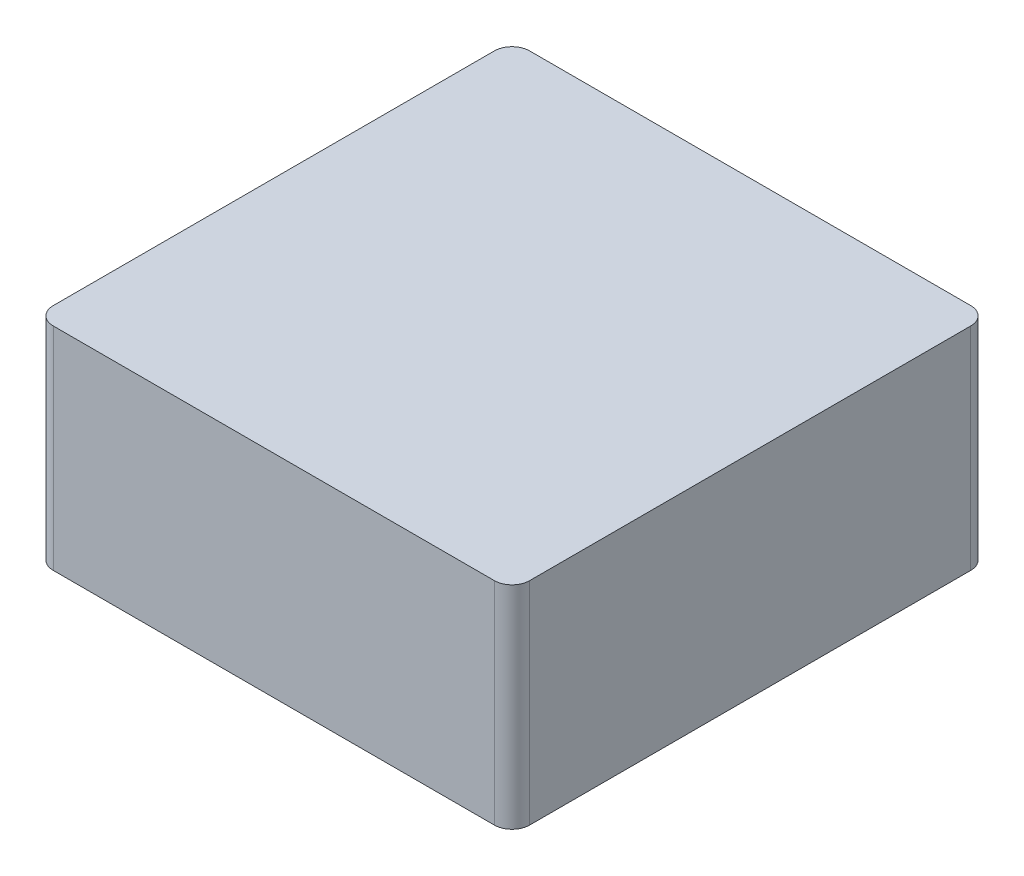
SolidWorks part; units mm, degrees
ref_plane "前视基准面" through (0, 0, 0) normal (0, 0, 1) x (1, 0, 0)
ref_plane "上视基准面" through (0, 0, 0) normal (0, 1, 0) x (1, 0, 0)
ref_plane "右视基准面" through (0, 0, 0) normal (1, 0, 0) x (0, 0, -1)
sketch "草图1" plane through (0, 0, 0) normal (0, 1, 0) x (1, 0, 0)
  line L1 (-27, 27) -> (27, 27)
  line L2 (-27, 27) -> (-27, -27)
  line L3 (-27, -27) -> (27, -27)
  line L4 (27, 27) -> (27, -27)
  line L5 (0, -27) -> (0, 27) construction
  line L6 (-27, 0) -> (27, 0) construction
  point P0 (0, 0)
  point P6 (-28.1217, -26.8398)
  dimension "D1" = 54
extrude "凸台-拉伸1" add sketch "草图1" along normal blind 24
fillet "圆角1" radius 2 1 edges at (-27, 12, 27)
fillet "圆角2" radius 2 1 edges at (-27, 12, -27)
fillet "圆角3" radius 2 1 edges at (27, 12, 27)
fillet "圆角4" radius 2 1 edges at (27, 12, -27)
sketch "草图6" plane through (0, 0, 0) normal (0, -1, 0) x (1, 0, 0)
  line L4 (-25.5, 25) -> (-25.5, -25)
  line L5 (-25, -25.5) -> (25, -25.5)
  line L6 (25.5, -25) -> (25.5, 25)
  line L7 (25, 25.5) -> (-25, 25.5)
  line L8 (27, -25) -> (27, 25)
  line L9 (-25, -27) -> (25, -27)
  line L10 (-27, 25) -> (-27, -25)
  line L11 (25, 27) -> (-25, 27)
  line L16 (27, -25) -> (27, 25)
  line L17 (-25, -27) -> (25, -27)
  line L18 (-27, 25) -> (-27, -25)
  line L19 (25, 27) -> (-25, 27)
  arc A4 (-25.5, -25) -> (-25, -25.5) centre (-25, -25) ccw
  arc A5 (25, -25.5) -> (25.5, -25) centre (25, -25) ccw
  arc A6 (25.5, 25) -> (25, 25.5) centre (25, 25) ccw
  arc A7 (25, -27) -> (27, -25) centre (25, -25) ccw
  arc A8 (25, -27) -> (27, -25) centre (25, -25) ccw
  arc A9 (-27, -25) -> (-25, -27) centre (-25, -25) ccw
  arc A10 (-27, -25) -> (-25, -27) centre (-25, -25) ccw
  arc A11 (27, 25) -> (25, 27) centre (25, 25) ccw
  arc A24 (27, 25) -> (25, 27) centre (25, 25) ccw
  arc A25 (-25, 25.5) -> (-25.5, 25) centre (-25, 25) ccw
  arc A26 (-25, 27) -> (-27, 25) centre (-25, 25) ccw
  arc A27 (-25, 27) -> (-27, 25) centre (-25, 25) ccw
  dimension "D1" = 0
  dimension "D2" = 1.5
extrude "切除-拉伸1" cut sketch "草图6" against normal blind 20 contours L7 A25 L4 A4 L5 A5 L6 A6 region at (0, 0, 0)
sketch "草图9" plane through (0, 20, 0) normal (0, -1, 0) x (1, 0, 0)
  line L0 (0, 0) -> (0, -27.9676)
  line L2 (-25, -25.5) -> (25, -25.5) construction
  circle A0 centre (-22.15, -22.5) radius 2.5
  circle A1 centre (-22.15, -22.5) radius 0.75
  circle A2 centre (22.15, -22.5) radius 0.75
  circle A3 centre (22.15, -22.5) radius 2.5
  circle A4 centre (22.15, 11.8) radius 2.5
  circle A5 centre (22.15, 11.8) radius 0.75
  circle A6 centre (-22.15, 11.8) radius 0.75
  circle A7 centre (-22.15, 11.8) radius 2.5
  point P17 (3.8015, -32.1874)
  dimension "D1" = 5
  dimension "D2" = 1.5
  dimension "D3" = 44.3
  dimension "D4" = 34.3
  dimension "D5" = 3
extrude "凸台-拉伸4" add sketch "草图9" along normal blind 6.4 contours A3 A2 | A0 A1 | A4 A5 | A7 A6 region at (-24.5793, 20, -22.5) region at (19.7207, 20, -22.5) region at (19.7207, 20, 11.8) region at (-24.5793, 20, 11.8)
